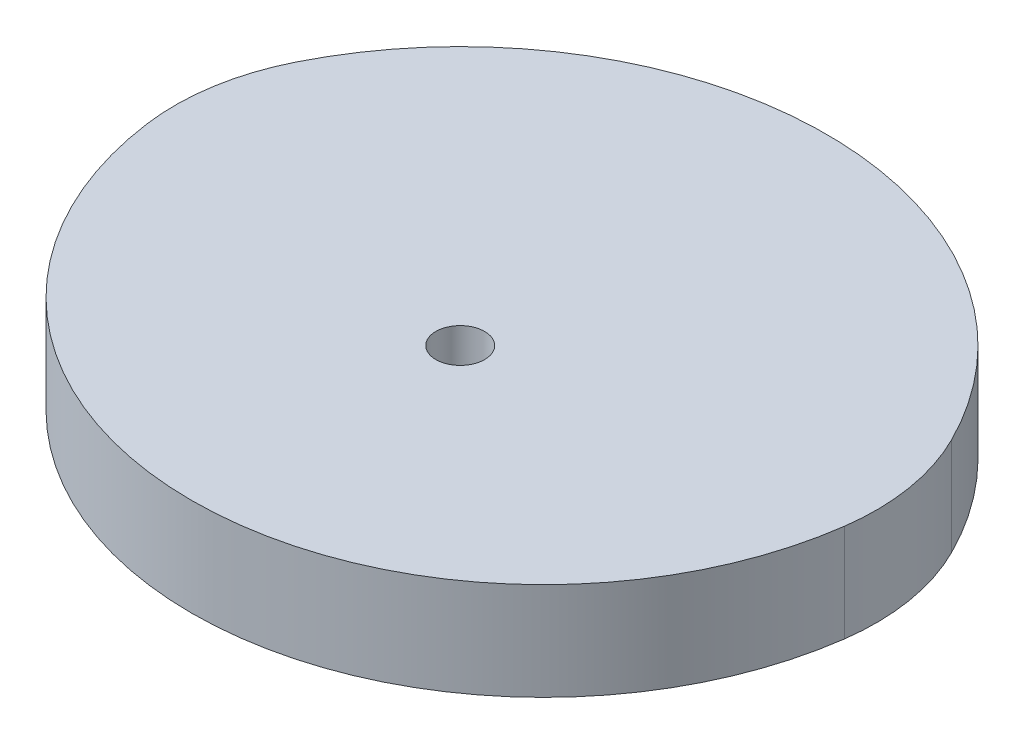
SolidWorks part; units mm, degrees
ref_plane "前视基准面" through (0, 0, 0) normal (0, 0, 1) x (1, 0, 0)
ref_plane "上视基准面" through (0, 0, 0) normal (0, 1, 0) x (1, 0, 0)
ref_plane "右视基准面" through (0, 0, 0) normal (1, 0, 0) x (0, 0, -1)
other "Configuration Table"
sketch "草图1" plane through (0, 0, 0) normal (0, 1, 0) x (1, 0, 0)
  line L0 (0, 60) -> (0, -40)
  arc A0 (53.6656, 26.8328) -> (-53.6656, 26.8328) centre (0, 0) ccw
  circle A2 centre (0, 0) radius 5
  arc A3 (0, 60) -> (53.6656, 26.8328) centre (0, 0) cw
  arc A6 (-56.5567, 9.3558) -> (56.5567, 9.3558) centre (0, 17.082) ccw
  arc A8 (-53.6656, 26.8328) -> (-56.5567, 9.3558) centre (-26.8328, 13.4164) ccw
  arc A9 (53.6656, 26.8328) -> (56.5567, 9.3558) centre (26.8328, 13.4164) cw
  arc A10 (62.6099, 31.305) -> (-62.6099, 31.305) centre (0, 0) ccw
  arc A11 (-62.6099, 31.305) -> (-66.4647, 8.0023) centre (-26.8328, 13.4164) ccw
  arc A12 (-66.4647, 8.0023) -> (66.4647, 8.0023) centre (0, 17.082) ccw
  arc A13 (62.6099, 31.305) -> (66.4647, 8.0023) centre (26.8328, 13.4164) cw
  arc A14 (44.7214, 22.3607) -> (-44.7214, 22.3607) centre (0, 0) ccw
  arc A15 (-44.7214, 22.3607) -> (-46.6488, 10.7094) centre (-26.8328, 13.4164) ccw
  arc A16 (-46.6488, 10.7094) -> (46.6488, 10.7094) centre (0, 17.082) ccw
  arc A17 (44.7214, 22.3607) -> (46.6488, 10.7094) centre (26.8328, 13.4164) cw
  arc A18 (67.082, 33.541) -> (71.4187, 7.3255) centre (26.8328, 13.4164) cw
  arc A19 (-71.4187, 7.3255) -> (71.4187, 7.3255) centre (0, 17.082) ccw
  arc A20 (-67.082, 33.541) -> (-71.4187, 7.3255) centre (-26.8328, 13.4164) ccw
  arc A21 (67.082, 33.541) -> (-67.082, 33.541) centre (0, 0) ccw
  point P8 (-57.0634, 18.541)
  dimension "D1" = 10
  dimension "D2" = 10
  dimension "D3" = 5
extrude "凸台-拉伸3" add sketch "草图1" along normal blind 20 contours A16 A15 A14 L0 A0 A8 A6 | A14 A17 A16 L0 A6 A9 A0 | A17 A14 L0 A2 A16 | A15 A16 L0 A2 A14 | A13 A10 A11 A12 A0 A9 A6 A8 | A18 A21 A20 A19 A10 A13 A12 A11 region at (30.9392, 0, -50.0606) region at (-1.1502, 0, -55) region at (19.7284, 0, -10.4405) region at (-19.7284, 0, -10.4405) region at (64.5243, 0, -19.6515) region at (69.3179, 0, -20.4444)
extrude "切除-拉伸2" cut sketch "草图1<4>" along normal blind 10 contours A13 A10 A11 A12 A0 A9 A6 A8 | A16 A15 A14 L0 A0 A8 A6 | A14 A17 A16 L0 A6 A9 A0 region at (30.9392, 0, -50.0606) region at (-1.1502, 0, -55) region at (64.5243, 0, -19.6515)
sketch "草图1<4>" plane through (0, 0, 0) normal (0, 1, 0) x (1, 0, 0) same geometry as "草图1"
